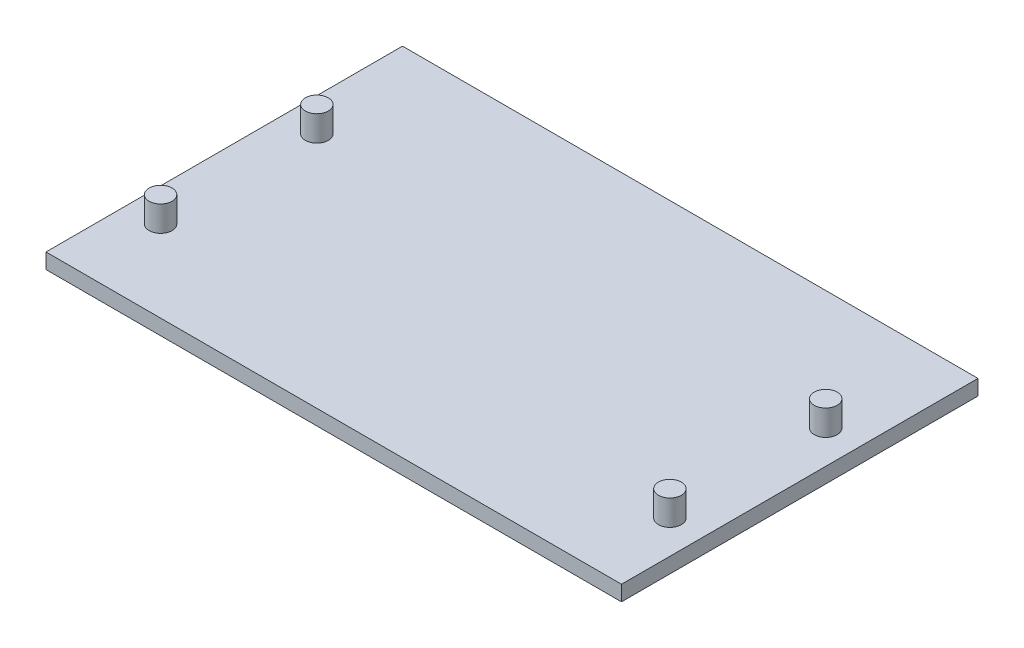
SolidWorks part; units mm, degrees
ref_plane "Front Plane" through (0, 0, 0) normal (0, 0, 1) x (1, 0, 0)
ref_plane "Top Plane" through (0, 0, 0) normal (0, 1, 0) x (1, 0, 0)
ref_plane "Right Plane" through (0, 0, 0) normal (1, 0, 0) x (0, 0, -1)
sketch "Sketch1" plane through (0, 0, 0) normal (0, 1, 0) x (1, 0, 0)
  line L1 (-52.5387, 40.0295) -> (60.4613, 40.0295)
  line L2 (-52.5387, 40.0295) -> (-52.5387, -29.9705)
  line L3 (-52.5387, -29.9705) -> (60.4613, -29.9705)
  line L4 (60.4613, 40.0295) -> (60.4613, -29.9705)
  dimension "D1" = 113
  dimension "D2" = 70
extrude "Boss-Extrude1" add sketch "Sketch1" along normal blind 3
sketch "Sketch2" plane through (0, 3, 0) normal (0, 1, 0) x (1, 0, 0)
  line L0 (60.4613, -29.9705) -> (60.4613, 40.0295) construction
  line L1 (-52.5387, -29.9705) -> (60.4613, -29.9705) construction
  circle A0 centre (-46.0387, 16.7095) radius 2.25
  circle A1 centre (53.9613, 16.6295) radius 2.25
  circle A2 centre (53.9613, -13.9705) radius 2.25
  circle A3 centre (-46.0387, -13.9705) radius 2.25
  point P10 (0, 0)
  dimension "D1" = 4.5
  dimension "D2" = 4.5
  dimension "D3" = 4.5
  dimension "D4" = 4.5
  dimension "D5" = 100
  dimension "D6" = 100
  dimension "D7" = 6.5
  dimension "D8" = 6.5
  dimension "D9" = 30.68
  dimension "D10" = 30.6
  dimension "D11" = 16
  dimension "D12" = 16
extrude "Boss-Extrude2" add sketch "Sketch2" along normal blind 5
